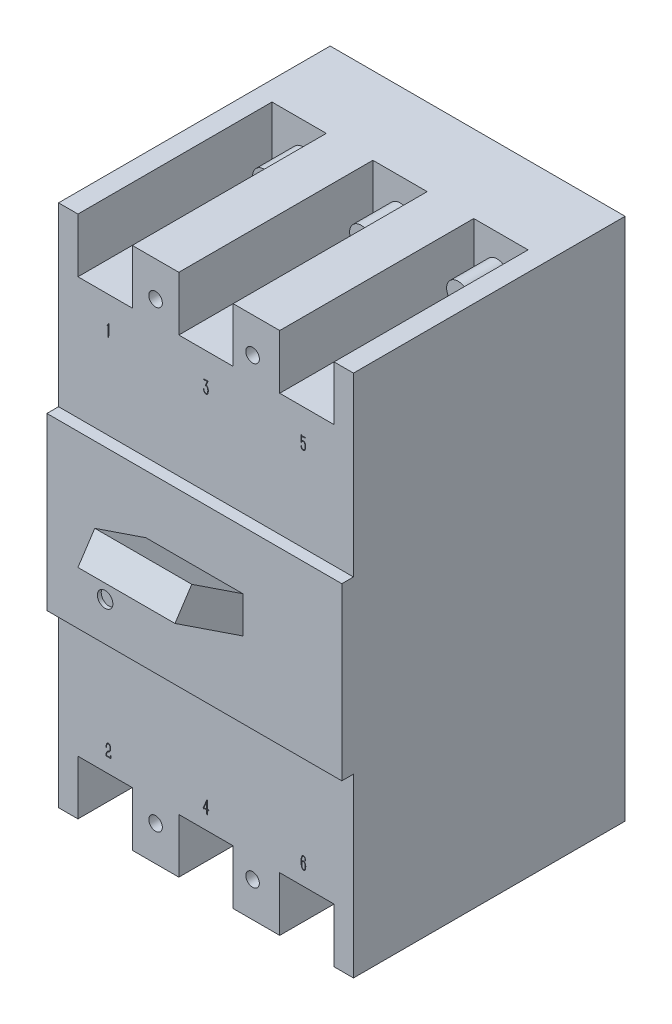
SolidWorks part; units mm, degrees
ref_plane "前视基准面" through (0, 0, 0) normal (0, 0, 1) x (1, 0, 0)
ref_plane "上视基准面" through (0, 0, 0) normal (0, 1, 0) x (1, 0, 0)
ref_plane "右视基准面" through (0, 0, 0) normal (1, 0, 0) x (0, 0, -1)
sketch "草图1" plane through (0, 0, 0) normal (0, 0, 1) x (1, 0, 0)
  line L1 (-38, 67.5) -> (38, 67.5)
  line L2 (-38, 67.5) -> (-38, -67.5)
  line L3 (-38, -67.5) -> (38, -67.5)
  line L4 (38, 67.5) -> (38, -67.5)
  line L5 (-38, 67.5) -> (38, -67.5) construction
  line L6 (-38, -67.5) -> (38, 67.5) construction
  point P0 (0, 0)
  dimension "D1" = 76
  dimension "D2" = 135
extrude "凸台-拉伸1" add sketch "草图1" along normal blind 73
sketch "草图2" plane through (0, 0, 73) normal (0, 0, 1) x (1, 0, 0)
  line L0 (38, -67.5) -> (38, 67.5) construction
  line L1 (-38, 67.5) -> (38, 67.5)
  line L2 (-38, 67.5) -> (-38, 22)
  line L3 (-38, 22) -> (38, 22)
  line L4 (38, 67.5) -> (38, 22)
  line L6 (49.775, 0) -> (-49.775, 0) construction
  dimension "D1" = 22
extrude "切除-拉伸1" cut sketch "草图2" against normal blind 3
mirror "镜向1" about plane through (0, 0, 0) normal (0, 1, 0) of "切除-拉伸1"
sketch "草图3" plane through (-38, 0, 0) normal (-1, 0, 0) x (0, 0, 1)
  line L0 (73, 7.0125) -> (86.167, 15.6969)
  line L2 (73, 22) -> (73, -22) construction
  line L3 (86.167, 15.6969) -> (90.5, 9.1274)
  line L4 (90.5, 9.1274) -> (73, -2.4149)
  line L6 (73, -2.4149) -> (73, 7.0125)
  line L7 (0, 67.5) -> (0, -67.5) construction
  dimension "D1" = 90.5
extrude "凸台-拉伸2" add sketch "草图3" along normal mid plane 25 from surface starting at plane "右视基准面"
sketch "草图4" plane through (0, 0, 70) normal (0, 0, 1) x (1, 0, 0)
  line L0 (19, 67.5) -> (19, 53.5)
  line L1 (38, 67.5) -> (-38, 67.5) construction
  line L2 (19, 53.5) -> (33, 53.5)
  line L3 (33, 53.5) -> (33, 67.5)
  line L4 (33, 67.5) -> (19, 67.5)
  line L5 (7, 67.5) -> (7, 53.5)
  line L6 (7, 53.5) -> (0, 53.5)
  line L7 (0, -40.15) -> (0, 40.15) construction
  line L8 (0, 53.5) -> (0, 67.5)
  line L9 (0, 67.5) -> (7, 67.5)
  dimension "D1" = 14
  dimension "D2" = 14
  dimension "D3" = 14
  dimension "D4" = 7
  dimension "D5" = 12
extrude "切除-拉伸2" cut sketch "草图4" against normal offset from surface (50 mm away) 20 up to face at (0, 0, 0)
mirror "镜向2" about plane through (0, 0, 0) normal (1, 0, 0) of "切除-拉伸2"
mirror "镜向3" about plane through (0, 0, 0) normal (0, 1, 0) of "切除-拉伸2", "镜向2"
sketch "草图5" plane through (0, 0, 20) normal (0, 0, 1) x (1, 0, 0)
  line L1 (-7, 67.5) -> (7, 67.5) construction
  line L2 (-38, 0) -> (59.3605, 0) construction
  line L3 (-38, 22) -> (-38, -22) construction
  circle A0 centre (25, 58.5) radius 3
  point P2 (0, 67.5)
  dimension "D1" = 6
  dimension "D2" = 25
  dimension "D3" = 117
sketch "草图6" plane through (0, 0, 20) normal (0, 0, 1) x (1, 0, 0)
  line L0 (0, -49.775) -> (0, 49.775) construction
  circle A0 centre (0, 58.5) radius 3
  dimension "D1" = 6
extrude "凸台-拉伸3" add sketch "草图5" along normal blind 10
extrude "凸台-拉伸4" add sketch "草图6" along normal blind 10
mirror "镜向4" about plane through (0, 0, 0) normal (1, 0, 0) of "凸台-拉伸3", "凸台-拉伸4"
mirror "镜向5" about plane through (0, 0, 0) normal (0, 1, 0) of "凸台-拉伸4", "凸台-拉伸3", "镜向4"
sketch "草图7" plane through (0, 0, 70) normal (0, 0, 1) x (1, 0, 0)
  line L0 (-41.8124, 0) -> (72.6215, 0) construction
  line L1 (41.8, 0) -> (-41.8, 0) construction
  line L2 (72.6215, 0) -> (66.5086, -8.4358) construction
  circle A0 centre (12, 58.5) radius 1.75
  circle A1 centre (-13, 58.5) radius 1.75
  dimension "D1" = 3.5
  dimension "D2" = 3.5
  dimension "D3" = 25
  dimension "D4" = 117
extrude "切除-拉伸3" cut sketch "草图7" against normal through all
mirror "镜向6" about plane through (0, 0, 0) normal (0, 1, 0) of "切除-拉伸3"
sketch "草图8" plane through (0, 0, 73) normal (0, 0, 1) x (1, 0, 0)
  line L0 (-38, -22) -> (38, -22) construction
  line L1 (-38, 22) -> (-38, -22) construction
  circle A0 centre (-23, -12) radius 2
  dimension "D3" = 4
  dimension "D1" = 10
  dimension "D2" = 15
extrude "切除-拉伸4" cut sketch "草图8" against normal blind 1
sketch "草图9" plane through (0, 0, 70) normal (0, 0, 1) x (1, 0, 0)
  line L0 (-26, 43.5) -> (26, 43.5) construction
  line L1 (-19, 53.5) -> (-33, 53.5) construction
  line L2 (-26, -50.1746) -> (26, -50.1746) construction
  text T0 "135\r\n"
  text T1 "246"
  dimension "D1" = 10
extrude "切除-拉伸5" cut sketch "草图9" against normal blind 1
sketch "0_0_Point" plane through (0, 0, 30) normal (0, 0, 1) x (1, 0, 0)
  point P0 (-25, 58.5)
sketch "1_0_Point" plane through (0, 0, 30) normal (0, 0, 1) x (1, 0, 0)
  point P0 (0, 58.5)
sketch "2_0_Point" plane through (0, 0, 30) normal (0, 0, 1) x (1, 0, 0)
  point P0 (25, 58.5)
sketch "0_1_Point" plane through (0, 0, 30) normal (0, 0, 1) x (1, 0, 0)
  point P0 (-25, -58.5)
sketch "1_1_Point" plane through (0, 0, 30) normal (0, 0, 1) x (1, 0, 0)
  point P0 (0, -58.5)
sketch "2_1_Point" plane through (0, 0, 30) normal (0, 0, 1) x (1, 0, 0)
  point P0 (25, -58.5)
other "0_0" parameters "直径"=2, "端头长度"=2
ref_axis "基准轴1" through (-25, 58.5, 40) along (0, 0, -1)
other "0_1" parameters "直径"=2, "端头长度"=2
ref_axis "基准轴2" through (-25, -58.5, 40) along (0, 0, -1)
other "1_0" parameters "直径"=2, "端头长度"=2
ref_axis "基准轴3" through (0, 58.5, 40) along (0, 0, -1)
other "1_1" parameters "直径"=2, "端头长度"=2
ref_axis "基准轴4" through (0, -58.5, 40) along (0, 0, -1)
other "2_0" parameters "直径"=2, "端头长度"=2
ref_axis "基准轴5" through (25, 58.5, 40) along (0, 0, -1)
other "2_1" parameters "直径"=2, "端头长度"=2
ref_axis "基准轴6" through (25, -58.5, 40) along (0, 0, -1)
